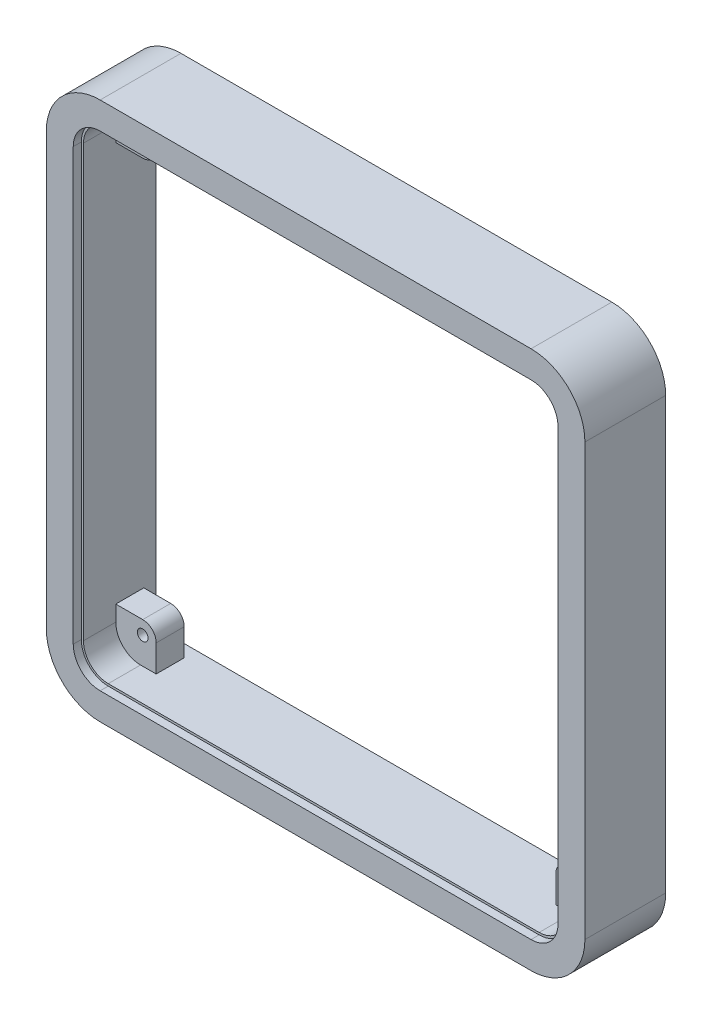
SolidWorks part; units mm, degrees
ref_plane "Piano frontale" through (0, 0, 0) normal (0, 0, 1) x (1, 0, 0)
ref_plane "Piano superiore" through (0, 0, 0) normal (0, 1, 0) x (1, 0, 0)
ref_plane "Piano destro" through (0, 0, 0) normal (1, 0, 0) x (0, 0, -1)
sketch "Sketch2" plane through (0, 0, 0) normal (0, 0, 1) x (1, 0, 0)
  line L5 (-100, -100) -> (100, -100)
  line L6 (-100, -100) -> (-100, 100)
  line L7 (-100, 100) -> (100, 100)
  line L8 (100, -100) -> (100, 100)
  line L9 (-100, -100) -> (100, 100) construction
  line L10 (-100, 100) -> (100, -100) construction
  point P0 (0, 0)
  dimension "D1" = 200
extrude "Boss-Extrude1" add sketch "Sketch2" along normal blind 30
fillet "Fillet1" radius 20 4 edges at (-100, -100, 15) (100, -100, 15) (100, 100, 15) (-100, 100, 15)
sketch "Sketch3" plane through (0, 0, 30) normal (0, 0, 1) x (1, 0, 0)
  line L8 (-90, 80) -> (-90, -80)
  line L9 (-80, -90) -> (80, -90)
  line L10 (90, -80) -> (90, 80)
  line L11 (80, 90) -> (-80, 90)
  line L12 (-90, 80) -> (-90, -80)
  line L13 (-80, -90) -> (80, -90)
  line L14 (90, -80) -> (90, 80)
  line L15 (80, 90) -> (-80, 90)
  arc A8 (-90, -80) -> (-80, -90) centre (-80, -80) ccw
  arc A9 (80, -90) -> (90, -80) centre (80, -80) ccw
  arc A10 (90, 80) -> (80, 90) centre (80, 80) ccw
  arc A11 (-80, 90) -> (-90, 80) centre (-80, 80) ccw
  arc A12 (-90, -80) -> (-80, -90) centre (-80, -80) ccw
  arc A13 (80, -90) -> (90, -80) centre (80, -80) ccw
  arc A14 (90, 80) -> (80, 90) centre (80, 80) ccw
  arc A15 (-80, 90) -> (-90, 80) centre (-80, 80) ccw
  dimension "D1" = 10
extrude "Cut-Extrude1" cut sketch "Sketch3" against normal blind 3
sketch "Sketch4" plane through (0, 0, 27) normal (0, 0, 1) x (1, 0, 0)
  line L16 (-89.2, 80) -> (-89.2, -80)
  line L17 (-80, -89.2) -> (80, -89.2)
  line L18 (89.2, -80) -> (89.2, 80)
  line L19 (80, 89.2) -> (-80, 89.2)
  line L20 (-89.2, 80) -> (-89.2, -80)
  line L21 (-80, -89.2) -> (80, -89.2)
  line L22 (89.2, -80) -> (89.2, 80)
  line L23 (80, 89.2) -> (-80, 89.2)
  arc A16 (-80, 89.2) -> (-89.2, 80) centre (-80, 80) ccw
  arc A17 (-89.2, -80) -> (-80, -89.2) centre (-80, -80) ccw
  arc A18 (80, -89.2) -> (89.2, -80) centre (80, -80) ccw
  arc A19 (89.2, 80) -> (80, 89.2) centre (80, 80) ccw
  arc A20 (-80, 89.2) -> (-89.2, 80) centre (-80, 80) ccw
  arc A21 (-89.2, -80) -> (-80, -89.2) centre (-80, -80) ccw
  arc A22 (80, -89.2) -> (89.2, -80) centre (80, -80) ccw
  arc A23 (89.2, 80) -> (80, 89.2) centre (80, 80) ccw
  dimension "D1" = 0.8
extrude "Cut-Extrude2" cut sketch "Sketch4" against normal through all
sketch "Sketch6" plane through (0, 0, 0) normal (0, 0, -1) x (-1, 0, 0)
  line L1 (-89.2, -74.2) -> (-74.2, -74.2)
  line L2 (-89.2, -74.2) -> (-89.2, -89.2)
  line L3 (-89.2, -89.2) -> (-74.2, -89.2)
  line L4 (-74.2, -74.2) -> (-74.2, -89.2)
  line L5 (-89.2, -80) -> (-89.2, 80) construction
  line L6 (80, -89.2) -> (-80, -89.2) construction
  line L18 (-74.2, 89.2) -> (-74.2, 74.2)
  line L19 (-89.2, 89.2) -> (89.2, 89.2) construction
  line L20 (-89.2, 89.2) -> (-89.2, -89.2) construction
  line L21 (-89.2, -89.2) -> (89.2, -89.2) construction
  line L22 (89.2, 89.2) -> (89.2, -89.2) construction
  line L23 (-89.2, 89.2) -> (89.2, -89.2) construction
  line L24 (-89.2, -89.2) -> (89.2, 89.2) construction
  line L25 (-74.2, 74.2) -> (-89.2, 74.2)
  line L26 (-89.2, 89.2) -> (-89.2, 74.2)
  line L27 (-74.2, 89.2) -> (-89.2, 89.2)
  line L28 (89.2, 74.2) -> (74.2, 74.2)
  line L29 (74.2, 74.2) -> (74.2, 89.2)
  line L30 (89.2, 89.2) -> (74.2, 89.2)
  line L31 (89.2, 74.2) -> (89.2, 89.2)
  line L32 (74.2, -89.2) -> (74.2, -74.2)
  line L33 (74.2, -74.2) -> (89.2, -74.2)
  line L34 (89.2, -89.2) -> (89.2, -74.2)
  line L35 (74.2, -89.2) -> (89.2, -89.2)
  point P14 (0, 0)
  point P19 (0, 0)
  point P24 (0, 0)
  point P29 (0, 0)
  dimension "D2" = 4
  dimension "D1" = 15
extrude "Boss-Extrude4" add sketch "Sketch6" against normal blind 15
fillet "Fillet2" radius 5 4 edges at (74.2, -74.2, 7.5) (-74.2, -74.2, 7.5) (-74.2, 74.2, 7.5) (74.2, 74.2, 7.5)
hole_wizard "Ø4.0 (4) Diameter Hole1" positions "Sketch8" profile "Sketch9" hole size "Ø4.0" standard "ANSI Metric" end condition through all
sketch "Sketch8" plane through (0, 0, 0) normal (0, 0, -1) x (-1, 0, 0)
  point P0 (-79.2, 79.2)
  point P3 (79.2, 79.2)
  point P6 (-79.2, -79.2)
  point P9 (79.2, -79.2)
sketch "Sketch9" plane through (79.2, 79.2, 0) normal (1, 0, 0) x (0, 1, 0)
  line L0 (0, 0) -> (0, 30)
  line L1 (0, 30) -> (2, 30)
  line L2 (2, 30) -> (2, 0)
  line L5 (2, 0) -> (0, 0)
  line L11 (0, -6.35) -> (0, 107.95) construction
  dimension "Thru Hole Dia." = 4
  dimension "Thru Hole Depth" = 30
sketch "Sketch10" plane through (0, 0, 0) normal (0, 0, -1) x (-1, 0, 0)
  line L0 (89.2, -80) -> (89.2, 80)
  line L1 (80, 89.2) -> (-80, 89.2)
  line L2 (-89.2, 80) -> (-89.2, -80)
  line L3 (-80, -89.2) -> (80, -89.2)
  line L4 (90, -80) -> (90, 80)
  line L5 (-80, -90) -> (80, -90)
  line L6 (-90, 80) -> (-90, -80)
  line L7 (80, 90) -> (-80, 90)
  line L8 (90, -80) -> (90, 80) construction
  line L9 (-80, -90) -> (80, -90) construction
  line L10 (-90, 80) -> (-90, -80) construction
  line L11 (80, 90) -> (-80, 90) construction
  arc A0 (89.2, 80) -> (80, 89.2) centre (80, 80) ccw
  arc A1 (-80, 89.2) -> (-89.2, 80) centre (-80, 80) ccw
  arc A2 (-89.2, -80) -> (-80, -89.2) centre (-80, -80) ccw
  arc A3 (80, -89.2) -> (89.2, -80) centre (80, -80) ccw
  arc A4 (90, 80) -> (80, 90) centre (80, 80) ccw
  arc A5 (80, -90) -> (90, -80) centre (80, -80) ccw
  arc A6 (-90, -80) -> (-80, -90) centre (-80, -80) ccw
  arc A7 (-80, 90) -> (-90, 80) centre (-80, 80) ccw
  arc A8 (90, 80) -> (80, 90) centre (80, 80) ccw construction
  arc A9 (80, -90) -> (90, -80) centre (80, -80) ccw construction
  arc A10 (-90, -80) -> (-80, -90) centre (-80, -80) ccw construction
  arc A11 (-80, 90) -> (-90, 80) centre (-80, 80) ccw construction
  dimension "D1" = 0
  dimension "D2" = 0.8
extrude "Cut-Extrude3" cut sketch "Sketch10" against normal blind 4.6
